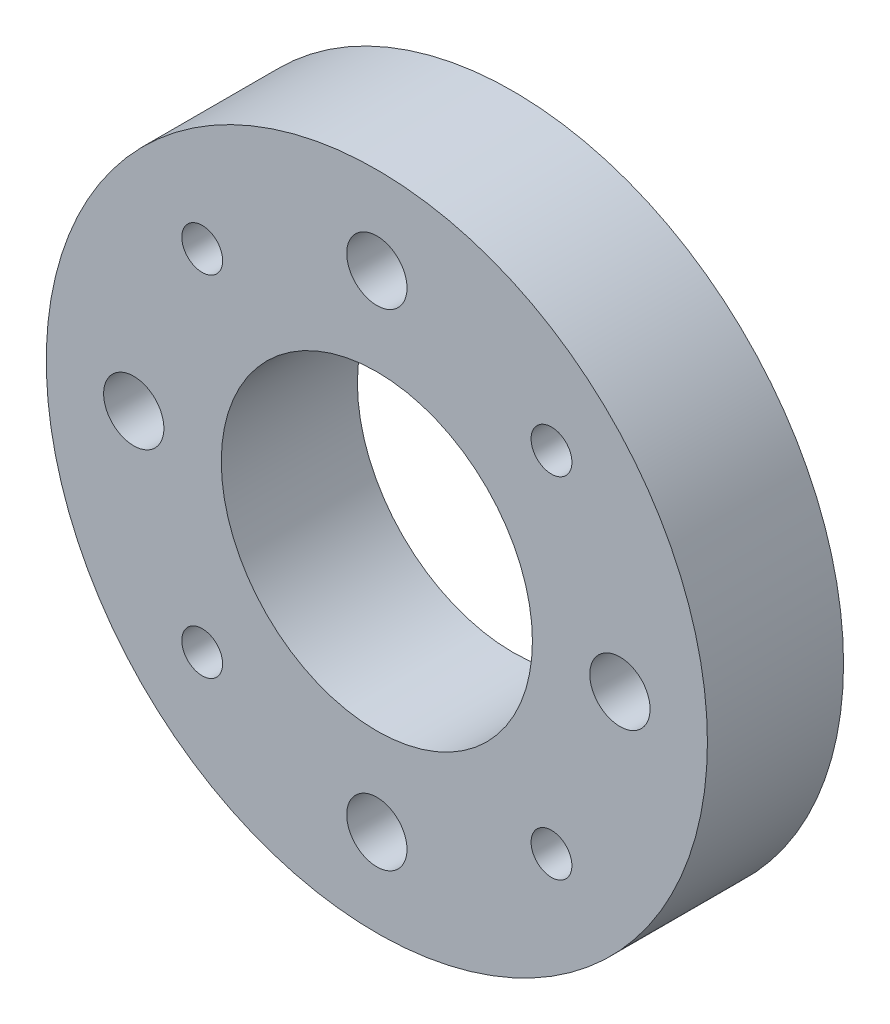
SolidWorks part; units mm, degrees
ref_plane "Front Plane" through (0, 0, 0) normal (0, 0, 1) x (1, 0, 0)
ref_plane "Top Plane" through (0, 0, 0) normal (0, 1, 0) x (1, 0, 0)
ref_plane "Right Plane" through (0, 0, 0) normal (1, 0, 0) x (0, 0, -1)
sketch "Sketch1" plane through (0, 0, 0) normal (0, 0, 1) x (1, 0, 0)
  circle A0 centre (0, 0) radius 17
  circle A1 centre (0, 0) radius 12.7 construction
  circle A2 centre (0, 0) radius 12.5 construction
  circle A3 centre (0, 12.5) radius 1.55
  circle A4 centre (12.5, 0) radius 1.55
  circle A5 centre (0, -12.5) radius 1.55
  circle A6 centre (-12.5, 0) radius 1.55
  circle A7 centre (-8.9803, 8.9803) radius 1.05
  circle A8 centre (8.9803, 8.9803) radius 1.05
  circle A9 centre (8.9803, -8.9803) radius 1.05
  circle A10 centre (-8.9803, -8.9803) radius 1.05
  circle A11 centre (0, 0) radius 8
  point P16 (0, 0)
  point P25 (0, 0)
  dimension "D1" = 4
  dimension "D2" = 4
extrude "Boss-Extrude1" add sketch "Sketch1" along normal blind 7
